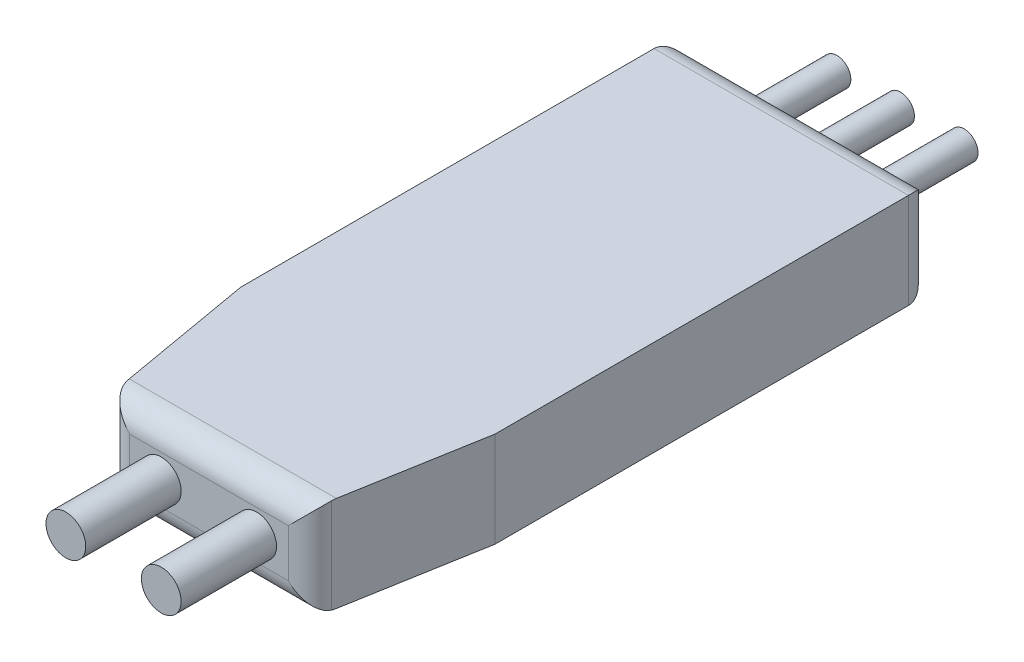
SolidWorks part; units mm, degrees
ref_plane "前视基准面" through (0, 0, 0) normal (0, 0, 1) x (1, 0, 0)
ref_plane "上视基准面" through (0, 0, 0) normal (0, 1, 0) x (1, 0, 0)
ref_plane "右视基准面" through (0, 0, 0) normal (1, 0, 0) x (0, 0, -1)
other "Configuration Table"
sketch "草图1" plane through (0, 0, 0) normal (0, 1, 0) x (1, 0, 0)
  line L0 (-16, 27.5) -> (16, 27.5)
  line L1 (-16, 27.5) -> (-16, -27.5)
  line L2 (16, 27.5) -> (16, -27.5)
  line L3 (-16, -27.5) -> (16, -27.5)
  line L4 (-16, 27.5) -> (16, -27.5) construction
  line L5 (16, 27.5) -> (-16, -27.5) construction
  line L6 (0, -27.5) -> (0, -47.5)
  line L7 (-12.5, -47.5) -> (12.5, -47.5)
  line L8 (-16, -27.5) -> (-12.5, -47.5)
  line L9 (12.5, -47.5) -> (16, -27.5)
  point P1 (0, 0)
  point P6 (0, -47.5)
  dimension "D1" = 32
  dimension "D2" = 55
  dimension "D3" = 20
  dimension "D4" = 12.5
extrude "凸台-拉伸1" add sketch "草图1" along normal blind 12 contours L1 L3 L2 L0 region at (0, 0, 0)
extrude "凸台-拉伸2" add sketch "草图1<3>" along normal blind 12 contours L3 L8 L7 L6 | L7 L9 L3 L6 region at (-7.1608, 0, 37.0906) region at (7.1608, 0, 37.0906)
sketch "草图1<3>" plane through (0, 0, 0) normal (0, 1, 0) x (1, 0, 0) same geometry as "草图1"
sketch "草图2" plane through (0, 0, 47.5) normal (0, 0, 1) x (1, 0, 0)
  line L0 (0, 0) -> (0, 12)
  line L1 (-12.5, 12) -> (12.5, 12) construction
  line L2 (-6, 6) -> (6, 6)
  circle A0 centre (6, 6) radius 2.5
  circle A1 centre (-6, 6) radius 2.5
  point P8 (0, 6)
  dimension "D1" = 5
  dimension "D2" = 5
extrude "凸台-拉伸3" add sketch "草图2" along normal blind 12 contours A0 | A1 region at (6, 8.4293, 47.5)
sketch "草图3" plane through (0, 0, -27.5) normal (0, 0, -1) x (-1, 0, 0)
  line L0 (0, 12) -> (0, 0)
  line L1 (16, 12) -> (-16, 12) construction
  circle A0 centre (0, 6) radius 1.75
  circle A1 centre (8, 6) radius 1.75
  circle A2 centre (-8, 6) radius 1.75
  dimension "D1" = 3.5
  dimension "D2" = 2
  dimension "D3" = 2
extrude "凸台-拉伸4" add sketch "草图3" along normal blind 12 contours L0 A0 | A1 | L0 A0 | A2 region at (-0.7427, 6, -27.5) region at (0.7427, 6, -27.5) region at (-8, 6, -27.5) region at (8, 6, -27.5)
fillet "圆角1" radius 3 8 edges at (0, 0, 47.5) (-12.5, 6, 47.5) (0, 12, 47.5) (12.5, 6, 47.5) (-16, 6, -27.5) (0, 0, -27.5) (0, 12, -27.5) (16, 6, -27.5)
